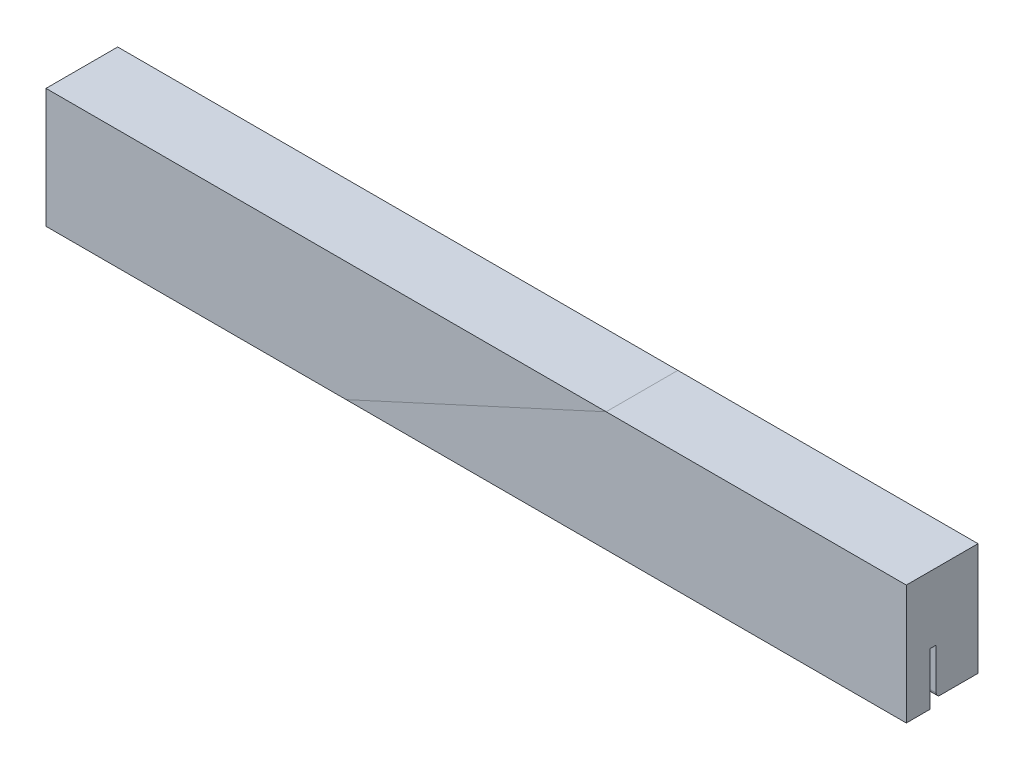
SolidWorks part; units mm, degrees
ref_plane "Front Plane" through (0, 0, 0) normal (0, 0, 1) x (1, 0, 0)
ref_plane "Top Plane" through (0, 0, 0) normal (0, 1, 0) x (1, 0, 0)
ref_plane "Right Plane" through (0, 0, 0) normal (1, 0, 0) x (0, 0, -1)
sketch "Sketch1" plane through (0, 0, 0) normal (0, 0, 1) x (1, 0, 0)
  line L1 (-114.3, -19.05) -> (114.3, -19.05)
  line L2 (-114.3, -19.05) -> (-114.3, 19.05)
  line L3 (-114.3, 19.05) -> (114.3, 19.05)
  line L4 (114.3, -19.05) -> (114.3, 19.05)
  line L5 (-114.3, -19.05) -> (114.3, 19.05) construction
  line L6 (-114.3, 19.05) -> (114.3, -19.05) construction
  line L7 (114.3, -12.7) -> (-114.3, -12.7)
  line L8 (114.3, -12.7) -> (114.3, 12.7)
  line L9 (114.3, 12.7) -> (-114.3, 12.7)
  line L10 (-114.3, -12.7) -> (-114.3, 12.7)
  line L11 (114.3, -12.7) -> (-114.3, 12.7) construction
  line L12 (114.3, 12.7) -> (-114.3, -12.7) construction
  point P0 (0, 0)
  point P6 (0, 0)
  dimension "D1" = 38.1
  dimension "D2" = 25.4
  dimension "D3" = 228.6
extrude "Boss-Extrude1" add sketch "Sketch1" along normal blind 6.35 contours L4 L9 L2 L7 | L9 L4 L3 L2 region at (0, 0, 0) region at (0, 15.875, 0)
extrude "Boss-Extrude2" add sketch "Sketch1<3>" against normal blind 12.7 contours L9 L4 L3 L2 region at (0, 15.875, 0)
sketch "Sketch1<3>" plane through (0, 0, 0) normal (0, 0, 1) x (1, 0, 0) same geometry as "Sketch1"
sketch "Sketch3" plane through (0, 0, 6.35) normal (0, 0, 1) x (1, 0, 0)
  line L0 (0, 19.05) -> (0, -12.7) construction
  line L1 (-114.3, 19.05) -> (114.3, 19.05) construction
  line L2 (114.3, -12.7) -> (-114.3, -12.7) construction
  line L3 (-34.5426, -12.7) -> (34.5426, 19.05)
  point P8 (0, 3.175)
  point P9 (34.5426, 19.05)
sketch "Sketch4" plane through (-114.3, 0, 0) normal (-1, 0, 0) x (0, 0, 1)
  line L0 (-12.7, 12.7) -> (-12.7, -10.795)
  line L2 (-1.6002, 1.27) -> (0, 1.27)
  line L3 (0, -12.7) -> (0, 12.7) construction
  line L4 (-1.6002, -10.795) -> (-12.7, -10.795)
  line L6 (0, 12.7) -> (0, -12.7)
  line L7 (0, -12.7) -> (6.35, -12.7)
  line L8 (6.35, -12.7) -> (6.35, 19.05)
  line L9 (6.35, 19.05) -> (-12.7, 19.05)
  line L10 (-12.7, 19.05) -> (-12.7, 12.7)
  line L11 (-12.7, 12.7) -> (0, 12.7)
  line L13 (0, -12.7) -> (6.35, -12.7)
  line L14 (6.35, -12.7) -> (6.35, 19.05)
  line L15 (6.35, 19.05) -> (-12.7, 19.05)
  line L16 (-12.7, 19.05) -> (-12.7, 12.7)
  line L20 (0, 1.27) -> (0, -12.7)
  line L21 (-1.6002, -10.795) -> (-1.6002, 1.27)
  point P4 (0, 0)
  dimension "D2" = 13.97
  dimension "D3" = 12.065
  dimension "D4" = 1.6002
  dimension "D1" = 0
extrude "Boss-Extrude3" add sketch "Sketch4" against normal up to surface (228.6 mm away) contours L13 L14 L15 L16 L0 L4 L21 L2 L20 up to face at (114.3, 6.35, -2.1167)
fillet "Fillet1" radius 1.016 1 edges at (0, -10.795, -1.6002)
split "Split2" trim tools "Sketch3" bodies to split 107 resulting bodies 108 109
